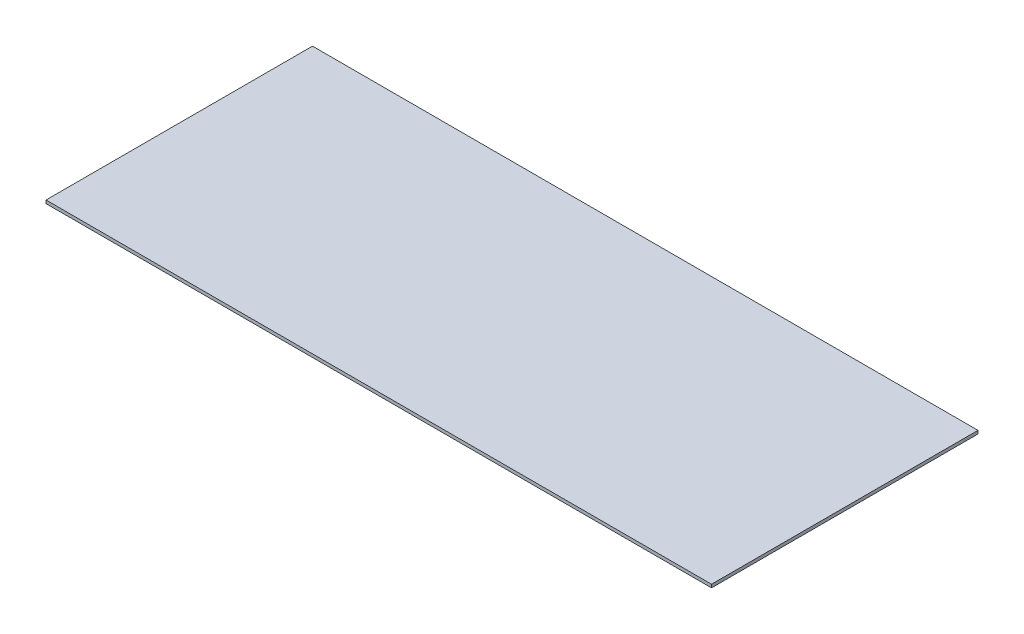
SolidWorks part; units mm, degrees
ref_plane "Front Plane" through (0, 0, 0) normal (0, 0, 1) x (1, 0, 0)
ref_plane "Top of Plywood" through (0, 0, 0) normal (0, 1, 0) x (1, 0, 0)
ref_plane "Right Plane" through (0, 0, 0) normal (1, 0, 0) x (0, 0, -1)
sketch "Interior Dim" plane through (0, 0, 0) normal (0, 1, 0) x (1, 0, 0)
  line L1 (0, 0) -> (5867.4, 0)
  line L2 (0, 0) -> (0, 2349.5)
  line L3 (0, 2349.5) -> (5867.4, 2349.5)
  line L4 (5867.4, 0) -> (5867.4, 2349.5)
  dimension "D1" = 5867.4
  dimension "D2" = 2349.5
sketch "Stud Centerlines" plane through (0, 0, 0) normal (0, 1, 0) x (1, 0, 0)
  line L0 (19.05, 19.05) -> (19.05, 2330.45) construction
  line L1 (19.05, 2330.45) -> (5867.4, 2330.45) construction
  line L2 (5867.4, 0) -> (5867.4, 2349.5) construction
  line L3 (5867.4, 19.05) -> (19.05, 19.05) construction
  line L4 (0, 0) -> (0, 2349.5) construction
  line L5 (0, 2349.5) -> (5867.4, 2349.5) construction
  line L6 (0, 0) -> (5867.4, 0) construction
  line L8 (4121.15, 2330.45) -> (4121.15, 19.05) construction
  line L9 (1797.05, 2330.45) -> (1797.05, 19.05) construction
  line L10 (19.05, 2051.05) -> (4121.15, 2051.05) construction
  dimension "D1" = 19.05
  dimension "D2" = 19.05
  dimension "D3" = 19.05
  dimension "D5" = 279.4
  dimension "D6" = 1778
  dimension "D7" = 2324.1
sketch "Gypsum Board" plane through (0, 0, 0) normal (0, 1, 0) x (1, 0, 0)
  line L0 (38.1, 38.1) -> (38.1, 2311.4)
  line L1 (38.1, 2311.4) -> (5867.4, 2311.4)
  line L2 (5867.4, 0) -> (5867.4, 2349.5) construction
  line L3 (50.8, 2298.7) -> (50.8, 50.8)
  line L4 (38.1, 38.1) -> (5867.4, 38.1)
  line L5 (50.8, 50.8) -> (5867.4, 50.8)
  line L6 (19.05, 19.05) -> (19.05, 2330.45) construction
  line L7 (19.05, 2330.45) -> (5867.4, 2330.45) construction
  line L8 (5867.4, 19.05) -> (19.05, 19.05) construction
  line L9 (4165.6, 50.8) -> (4165.6, 2095.5)
  line L10 (50.8, 2298.7) -> (5867.4, 2298.7)
  line L11 (4165.6, 2095.5) -> (4178.3, 2095.5)
  line L12 (4178.3, 2095.5) -> (4178.3, 50.8)
  line L13 (4121.15, 2330.45) -> (4121.15, 19.05) construction
  line L14 (19.05, 2051.05) -> (4121.15, 2051.05) construction
  line L15 (5867.4, 2311.4) -> (5867.4, 2298.7)
  line L16 (5867.4, 50.8) -> (5867.4, 38.1)
  line L17 (4165.6, 50.8) -> (4178.3, 50.8)
  dimension "D1" = 19.05
  dimension "D2" = 19.05
  dimension "D3" = 12.7
  dimension "D4" = 12.7
  dimension "D5" = 12.7
  dimension "D6" = 19.05
  dimension "D7" = 44.45
  dimension "D8" = 12.7
  dimension "D9" = 44.45
sketch "PVC" plane through (0, 0, 0) normal (0, 1, 0) x (1, 0, 0)
  line L0 (50.8, 50.8) -> (50.8, 2006.6)
  line L1 (4076.7, 50.8) -> (1841.5, 50.8)
  line L2 (50.8, 50.8) -> (1752.6, 50.8)
  line L3 (1752.6, 50.8) -> (1752.6, 2006.6)
  line L4 (1752.6, 2006.6) -> (50.8, 2006.6)
  line L5 (50.8, 2298.7) -> (50.8, 50.8) construction
  line L6 (19.05, 2051.05) -> (4121.15, 2051.05) construction
  line L7 (1797.05, 2330.45) -> (1797.05, 19.05) construction
  line L8 (50.8, 50.8) -> (5867.4, 50.8) construction
  line L9 (63.5, 1993.9) -> (1739.9, 1993.9)
  line L10 (1739.9, 1993.9) -> (1739.9, 63.5)
  line L11 (1739.9, 63.5) -> (63.5, 63.5)
  line L12 (63.5, 63.5) -> (63.5, 1993.9)
  line L13 (1841.5, 2006.6) -> (4076.7, 2006.6)
  line L14 (4076.7, 2006.6) -> (4076.7, 50.8)
  line L15 (1841.5, 50.8) -> (1841.5, 2006.6)
  line L16 (4121.15, 2330.45) -> (4121.15, 19.05) construction
  line L17 (1854.2, 1993.9) -> (1854.2, 63.5)
  line L18 (1854.2, 63.5) -> (4064, 63.5)
  line L19 (4064, 63.5) -> (4064, 1993.9)
  line L20 (4064, 1993.9) -> (1854.2, 1993.9)
  dimension "D1" = 0
  dimension "D2" = 44.45
  dimension "D3" = 44.45
  dimension "D4" = 0
  dimension "D5" = 12.7
  dimension "D6" = 12.7
  dimension "D7" = 12.7
  dimension "D8" = 12.7
  dimension "D9" = 44.45
  dimension "D10" = 44.45
  dimension "D11" = 12.7
  dimension "D12" = 12.7
  dimension "D13" = 12.7
  dimension "D14" = 12.7
sketch "Open Indoor Space" plane through (0, 0, 0) normal (0, 1, 0) x (1, 0, 0)
  line L0 (4178.3, 2095.5) -> (4165.6, 2095.5)
  line L1 (63.5, 63.5) -> (1739.9, 63.5)
  line L2 (63.5, 63.5) -> (63.5, 1993.9)
  line L3 (63.5, 1993.9) -> (1739.9, 1993.9)
  line L4 (1739.9, 63.5) -> (1739.9, 1993.9)
  line L5 (1854.2, 63.5) -> (4064, 63.5)
  line L6 (1854.2, 63.5) -> (1854.2, 1993.9)
  line L7 (1854.2, 1993.9) -> (4064, 1993.9)
  line L8 (4064, 63.5) -> (4064, 1993.9)
  line L9 (4165.6, 2095.5) -> (50.8, 2095.5)
  line L10 (50.8, 2298.7) -> (50.8, 50.8) construction
  line L11 (50.8, 2095.5) -> (50.8, 2298.7)
  line L12 (50.8, 2298.7) -> (5867.4, 2298.7)
  line L13 (5867.4, 2298.7) -> (5867.4, 50.8)
  line L14 (5867.4, 50.8) -> (4178.3, 50.8)
  line L15 (4178.3, 50.8) -> (4178.3, 2095.5)
ref_plane "Interior Roof" through (0, 2381.25, 0) normal (0, 1, 0) x (1, 0, 0)
sketch "Sketch4" plane through (0, 0, 0) normal (0, 1, 0) x (1, 0, 0)
  line L1 (0, 0) -> (5867.4, 0)
  line L2 (0, 0) -> (0, 2349.5)
  line L3 (0, 2349.5) -> (5867.4, 2349.5)
  line L4 (5867.4, 0) -> (5867.4, 2349.5)
extrude "Boss-Extrude2" add sketch "Sketch4" against normal blind 27.94
sketch "Sketch5" plane through (0, 0, 0) normal (0, 1, 0) x (1, 0, 0)
  line L0 (177.8, 63.5) -> (177.8, 0)
  line L1 (1739.9, 63.5) -> (63.5, 63.5) construction
  line L2 (0, 0) -> (5867.4, 0) construction
  line L3 (1168.4, 63.5) -> (1168.4, 0)
  line L4 (63.5, 63.5) -> (63.5, 1993.9) construction
  dimension "D1" = 990.6
  dimension "D2" = 114.3
ref_plane "Top of Interior Roof" through (0, 2133.6, 0) normal (0, 1, 0) x (1, 0, 0)
ref_plane "Top of Insulated Subfloor" through (0, 40.64, 0) normal (0, 1, 0) x (1, 0, 0)
ref_plane "Top of Vinyl Flooring" through (0, 43.815, 0) normal (0, 1, 0) x (1, 0, 0)
sketch "Bathroom Floorspace" plane through (0, 0, 0) normal (0, 1, 0) x (1, 0, 0)
  line L1 (63.5, 1993.9) -> (1739.9, 1993.9)
  line L2 (63.5, 1993.9) -> (63.5, 63.5)
  line L3 (63.5, 63.5) -> (1739.9, 63.5)
  line L4 (1739.9, 1993.9) -> (1739.9, 63.5)
  line L5 (1854.2, 1993.9) -> (4064, 1993.9)
  line L6 (1854.2, 1993.9) -> (1854.2, 63.5)
  line L7 (1854.2, 63.5) -> (4064, 63.5)
  line L8 (4064, 1993.9) -> (4064, 63.5)
